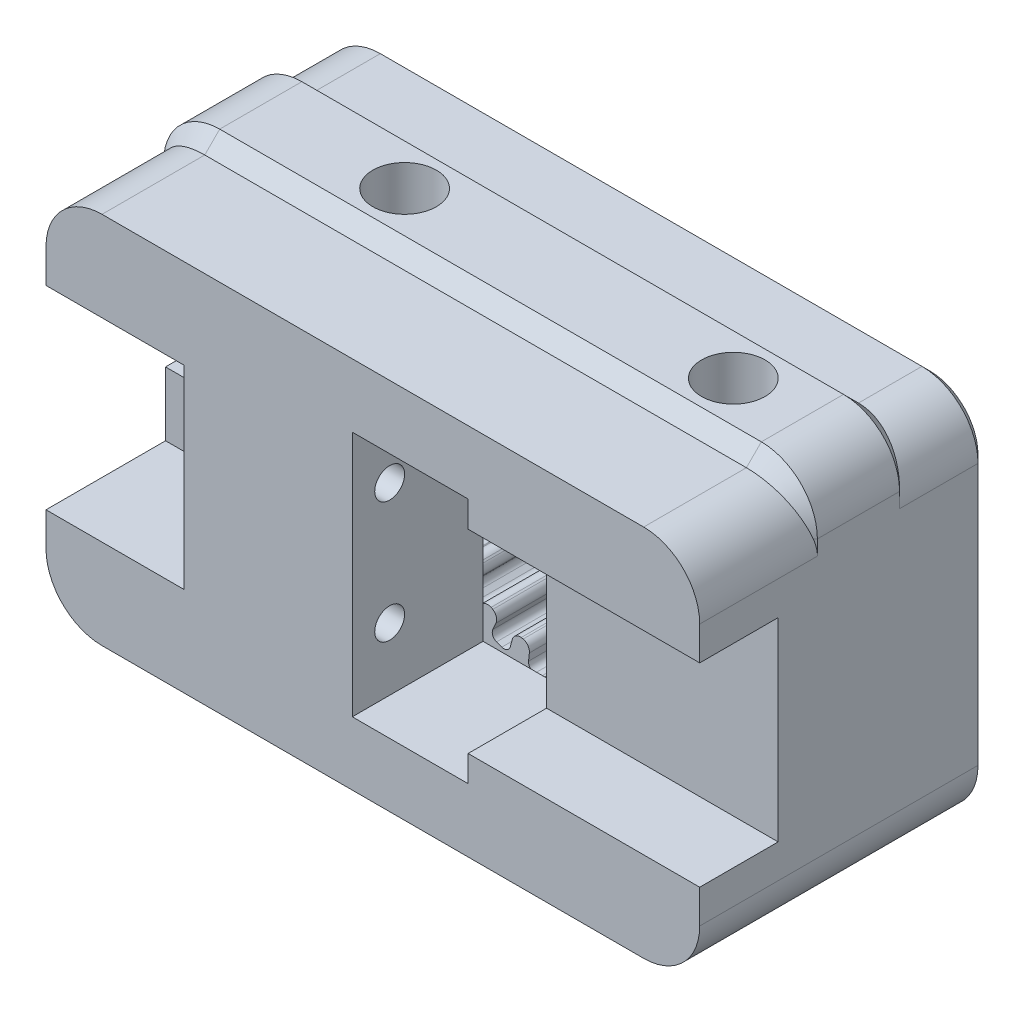
SolidWorks part; units mm, degrees
material "ABS"
ref_plane "Top Plane" through (0, 0, 0) normal (0, 0, 1) x (1, 0, 0)
ref_plane "Front Plane" through (0, 0, 0) normal (0, 1, 0) x (1, 0, 0)
ref_plane "Right Plane" through (0, 0, 0) normal (1, 0, 0) x (0, 0, -1)
sketch "Sketch1" plane through (0, 0, 0) normal (0, 0, 1) x (1, 0, 0)
  line L1 (-17.5, -10) -> (17.5, -10)
  line L2 (-17.5, -10) -> (-17.5, 10)
  line L3 (-17.5, 10) -> (17.5, 10)
  line L4 (17.5, -10) -> (17.5, 10)
  line L5 (-17.5, -10) -> (17.5, 10) construction
  line L6 (-17.5, 10) -> (17.5, -10) construction
  point P0 (0, 0)
  dimension "D1" = 35
  dimension "D2" = 20
extrude "Base" add sketch "Sketch1" along normal blind 15.3
sketch "Sketch2" plane through (0, 0, 15.3) normal (0, 0, 1) x (1, 0, 0)
  line L0 (-17.5, 10) -> (-17.5, -10) construction
  line L1 (-17.5, 5.2) -> (-10.1, 5.2)
  line L2 (-17.5, 5.2) -> (-17.5, -5.2)
  line L3 (-17.5, -5.2) -> (-10.1, -5.2)
  line L4 (-10.1, 5.2) -> (-10.1, -5.2)
  dimension "D1" = 7.4
  dimension "D2" = 10.4
  dimension "D3" = 5.2
extrude "plug cutout1" cut sketch "Sketch2" against normal blind 6.4
sketch "Sketch3" plane through (0, 0, 8.9) normal (0, 0, 1) x (1, 0, 0)
  line L0 (-17.5, 5.2) -> (-17.5, -5.2) construction
  line L1 (-17.5, 1.775) -> (-10.1, 1.775)
  line L2 (-17.5, 1.775) -> (-17.5, -1.775)
  line L3 (-17.5, -1.775) -> (-10.1, -1.775)
  line L4 (-10.1, 1.775) -> (-10.1, -1.775)
  line L5 (-10.1, -5.2) -> (-10.1, 5.2) construction
  dimension "D1" = 3.55
  dimension "D2" = 1.775
extrude "plug cutout 2" cut sketch "Sketch3" against normal blind 2.8
sketch "Sketch4" plane through (0, 0, 15.3) normal (0, 0, 1) x (1, 0, 0)
  line L0 (17.5, -10) -> (17.5, 10) construction
  line L1 (17.5, 5.2) -> (5.1, 5.2)
  line L2 (17.5, 5.2) -> (17.5, -5.2)
  line L3 (17.5, -5.2) -> (5.1, -5.2)
  line L4 (5.1, 5.2) -> (5.1, -5.2)
  dimension "D1" = 10.4
  dimension "D2" = 5.2
  dimension "D3" = 12.4
extrude "electronics cutout 1" cut sketch "Sketch4" against normal blind 4.2
sketch "Sketch5" plane through (0, 0, 15.3) normal (0, 0, 1) x (1, 0, 0)
  line L0 (5.1, 5.2) -> (5.1, -5.2) construction
  line L1 (-1.1, 6.6) -> (5.1, 6.6)
  line L2 (-1.1, 6.6) -> (-1.1, -6.6)
  line L3 (-1.1, -6.6) -> (5.1, -6.6)
  line L4 (5.1, 6.6) -> (5.1, -6.6)
  dimension "D1" = 6.2
  dimension "D2" = 13.2
  dimension "D3" = 6.6
  dimension "D4" = 0
extrude "switch cutout" cut sketch "Sketch5" against normal blind 7
sketch "Sketch6" plane through (-1.1, 0, 0) normal (1, 0, 0) x (0, 0, -1)
  line L0 (-15.3, 6.6) -> (-15.3, -6.6) construction
  circle A0 centre (-13.3, 3.25) radius 0.8
  circle A1 centre (-13.3, -3.25) radius 0.8
  dimension "D1" = 1.6
  dimension "D2" = 1.6
  dimension "D3" = 6.5
  dimension "D4" = 3.25
  dimension "D5" = 2
  dimension "D6" = 2
extrude "switch screwholes" cut sketch "Sketch6" against normal blind 4.5
sketch "Sketch7" plane through (0, 0, 0) normal (0, 0, -1) x (-1, 0, 0)
  circle A0 centre (-2, 0) radius 5.5
  dimension "D1" = 11
  dimension "D2" = 2
extrude "Cut-Extrude6" cut sketch "Sketch7" against normal blind 8.3
chamfer "Chamfer1" distance 1.2 angle 45 1 edges at (-3.5, 0, 0)
sketch "Sketch9" plane through (0, 0, 0) normal (0, 0, -1) x (-1, 0, 0)
  line L0 (-2, 0) -> (-2.1763, 6.6977) construction
  line L1 (-2, 0) -> (-0.098, 6.4243) construction
  line L2 (-2, 0) -> (-1.6503, 6.6909) construction
  line L3 (-2, 0) -> (-0.6079, 6.5538) construction
  line L4 (-1.6693, 6.3264) -> (-1.6904, 5.9232)
  line L5 (-0.6837, 6.1968) -> (-0.7676, 5.8019)
  line L6 (0.2695, 5.9146) -> (0.1248, 5.5376)
  line L7 (1.1668, 5.4868) -> (0.965, 5.1371)
  line L8 (1.9861, 4.9238) -> (1.7321, 4.61)
  line L9 (2.7073, 4.2396) -> (2.4073, 3.9694)
  line L10 (3.3126, 3.451) -> (2.974, 3.2311)
  line L11 (3.787, 2.5775) -> (3.4182, 2.4132)
  line L12 (4.119, 1.6405) -> (3.729, 1.5359)
  line L13 (4.3003, 0.663) -> (3.8987, 0.6208)
  line L14 (4.3264, -0.3307) -> (3.9232, -0.3096)
  line L15 (4.1968, -1.3163) -> (3.8019, -1.2324)
  line L16 (3.9146, -2.2695) -> (3.5376, -2.1248)
  line L17 (3.4868, -3.1668) -> (3.1371, -2.965)
  line L18 (2.9238, -3.9861) -> (2.61, -3.7321)
  line L19 (2.2396, -4.7073) -> (1.9694, -4.4073)
  line L20 (1.451, -5.3126) -> (1.2311, -4.974)
  line L21 (0.5775, -5.787) -> (0.4132, -5.4182)
  line L22 (-0.3595, -6.119) -> (-0.4641, -5.729)
  line L23 (-1.337, -6.3003) -> (-1.3792, -5.8987)
  line L24 (-2.3307, -6.3264) -> (-2.3096, -5.9232)
  line L25 (-3.3163, -6.1968) -> (-3.2324, -5.8019)
  line L26 (-4.2695, -5.9146) -> (-4.1248, -5.5376)
  line L27 (-5.1668, -5.4868) -> (-4.965, -5.1371)
  line L28 (-5.9861, -4.9238) -> (-5.7321, -4.61)
  line L29 (-6.7073, -4.2396) -> (-6.4073, -3.9694)
  line L30 (-7.3126, -3.451) -> (-6.974, -3.2311)
  line L31 (-7.787, -2.5775) -> (-7.4182, -2.4132)
  line L32 (-8.119, -1.6405) -> (-7.729, -1.5359)
  line L33 (-8.3003, -0.663) -> (-7.8987, -0.6208)
  line L34 (-8.3264, 0.3307) -> (-7.9232, 0.3096)
  line L35 (-8.1968, 1.3163) -> (-7.8019, 1.2324)
  line L36 (-7.9146, 2.2695) -> (-7.5376, 2.1248)
  line L37 (-7.4868, 3.1668) -> (-7.1371, 2.965)
  line L38 (-6.9238, 3.9861) -> (-6.61, 3.7321)
  line L39 (-6.2396, 4.7073) -> (-5.9694, 4.4073)
  line L40 (-5.451, 5.3126) -> (-5.2311, 4.974)
  line L41 (-4.5775, 5.787) -> (-4.4132, 5.4182)
  line L42 (-3.6405, 6.119) -> (-3.5359, 5.729)
  line L43 (-2.663, 6.3003) -> (-2.6208, 5.8987)
  circle A0 centre (-2, 0) radius 6.7 construction
  arc A1 (-2.1763, 6.6977) -> (-2.0251, 6.7) centre (-2, 0) cw
  arc A2 (-0.2434, 6.4656) -> (-0.098, 6.4243) centre (-2, 0) cw
  arc A3 (-1.2984, 5.4534) -> (-1.2677, 5.4494) centre (-2, 0) cw
  arc A4 (-0.2434, 6.4656) -> (-0.6837, 6.1968) centre (-0.3364, 6.123) ccw
  arc A5 (-2.0251, 6.7) -> (-1.6693, 6.3264) centre (-2.0238, 6.345) cw
  arc A6 (-1.2677, 5.4494) -> (-0.7676, 5.8019) centre (-1.2078, 5.8954) ccw
  arc A7 (-1.2984, 5.4534) -> (-1.6904, 5.9232) centre (-1.241, 5.8997) cw
  arc A8 (-0.098, 6.4243) -> (0.0465, 6.3798) centre (-2, 0) cw
  arc A9 (1.6686, 5.6063) -> (1.7942, 5.5222) centre (-2, 0) cw
  arc A10 (0.3524, 4.9697) -> (0.3804, 4.9564) centre (-2, 0) cw
  arc A11 (1.6686, 5.6063) -> (1.1668, 5.4868) centre (1.4743, 5.3093) ccw
  arc A12 (0.0465, 6.3798) -> (0.2695, 5.9146) centre (-0.062, 6.0418) cw
  arc A13 (0.3804, 4.9564) -> (0.965, 5.1371) centre (0.5752, 5.362) ccw
  arc A14 (0.3524, 4.9697) -> (0.1248, 5.5376) centre (0.545, 5.3764) cw
  arc A15 (1.7942, 5.5222) -> (1.9178, 5.4352) centre (-2, 0) cw
  arc A16 (3.2215, 4.1983) -> (3.3149, 4.0794) centre (-2, 0) cw
  arc A17 (1.773, 3.9995) -> (1.7955, 3.9782) centre (-2, 0) cw
  arc A18 (3.2215, 4.1983) -> (2.7073, 4.2396) centre (2.9449, 3.9758) ccw
  arc A19 (1.9178, 5.4352) -> (1.9861, 4.9238) centre (1.7102, 5.1472) cw
  arc A20 (1.7955, 3.9782) -> (2.4073, 3.9694) centre (2.1061, 4.3038) ccw
  arc A21 (1.773, 3.9995) -> (1.7321, 4.61) centre (2.0818, 4.3269) cw
  arc A22 (3.3149, 4.0794) -> (3.4056, 3.9585) centre (-2, 0) cw
  arc A23 (4.2633, 2.3793) -> (4.3154, 2.2374) centre (-2, 0) cw
  arc A24 (2.8243, 2.6378) -> (2.8391, 2.6106) centre (-2, 0) cw
  arc A25 (4.2633, 2.3793) -> (3.787, 2.5775) centre (3.9315, 2.2532) ccw
  arc A26 (3.4056, 3.9585) -> (3.3126, 3.451) centre (3.1192, 3.7487) cw
  arc A27 (2.8391, 2.6106) -> (3.4182, 2.4132) centre (3.2351, 2.8243) ccw
  arc A28 (2.8243, 2.6378) -> (2.974, 3.2311) centre (3.2191, 2.8537) cw
  arc A29 (4.3154, 2.2374) -> (4.3643, 2.0943) centre (-2, 0) cw
  arc A30 (4.692, 0.3273) -> (4.6977, 0.1763) centre (-2, 0) cw
  arc A31 (3.4033, 1.0179) -> (3.409, 0.9875) centre (-2, 0) cw
  arc A32 (4.692, 0.3273) -> (4.3003, 0.663) centre (4.3374, 0.31) ccw
  arc A33 (4.3643, 2.0943) -> (4.119, 1.6405) centre (4.0271, 1.9834) cw
  arc A34 (3.409, 0.9875) -> (3.8987, 0.6208) centre (3.8516, 1.0683) ccw
  arc A35 (3.4033, 1.0179) -> (3.729, 1.5359) centre (3.8455, 1.1013) cw
  arc A36 (4.6977, 0.1763) -> (4.7, 0.0251) centre (-2, 0) cw
  arc A37 (4.4656, -1.7566) -> (4.4243, -1.902) centre (-2, 0) cw
  arc A38 (3.4534, -0.7016) -> (3.4494, -0.7323) centre (-2, 0) cw
  arc A39 (4.4656, -1.7566) -> (4.1968, -1.3163) centre (4.123, -1.6636) ccw
  arc A40 (4.7, 0.0251) -> (4.3264, -0.3307) centre (4.345, 0.0238) cw
  arc A41 (3.4494, -0.7323) -> (3.8019, -1.2324) centre (3.8954, -0.7922) ccw
  arc A42 (3.4534, -0.7016) -> (3.9232, -0.3096) centre (3.8997, -0.759) cw
  arc A43 (4.4243, -1.902) -> (4.3798, -2.0465) centre (-2, 0) cw
  arc A44 (3.6063, -3.6686) -> (3.5222, -3.7942) centre (-2, 0) cw
  arc A45 (2.9697, -2.3524) -> (2.9564, -2.3804) centre (-2, 0) cw
  arc A46 (3.6063, -3.6686) -> (3.4868, -3.1668) centre (3.3093, -3.4743) ccw
  arc A47 (4.3798, -2.0465) -> (3.9146, -2.2695) centre (4.0418, -1.938) cw
  arc A48 (2.9564, -2.3804) -> (3.1371, -2.965) centre (3.362, -2.5752) ccw
  arc A49 (2.9697, -2.3524) -> (3.5376, -2.1248) centre (3.3764, -2.545) cw
  arc A50 (3.5222, -3.7942) -> (3.4352, -3.9178) centre (-2, 0) cw
  arc A51 (2.1983, -5.2215) -> (2.0794, -5.3149) centre (-2, 0) cw
  arc A52 (1.9995, -3.773) -> (1.9782, -3.7955) centre (-2, 0) cw
  arc A53 (2.1983, -5.2215) -> (2.2396, -4.7073) centre (1.9758, -4.9449) ccw
  arc A54 (3.4352, -3.9178) -> (2.9238, -3.9861) centre (3.1472, -3.7102) cw
  arc A55 (1.9782, -3.7955) -> (1.9694, -4.4073) centre (2.3038, -4.1061) ccw
  arc A56 (1.9995, -3.773) -> (2.61, -3.7321) centre (2.3269, -4.0818) cw
  arc A57 (2.0794, -5.3149) -> (1.9585, -5.4056) centre (-2, 0) cw
  arc A58 (0.3793, -6.2633) -> (0.2374, -6.3154) centre (-2, 0) cw
  arc A59 (0.6378, -4.8243) -> (0.6106, -4.8391) centre (-2, 0) cw
  arc A60 (0.3793, -6.2633) -> (0.5775, -5.787) centre (0.2532, -5.9315) ccw
  arc A61 (1.9585, -5.4056) -> (1.451, -5.3126) centre (1.7487, -5.1192) cw
  arc A62 (0.6106, -4.8391) -> (0.4132, -5.4182) centre (0.8243, -5.2351) ccw
  arc A63 (0.6378, -4.8243) -> (1.2311, -4.974) centre (0.8537, -5.2191) cw
  arc A64 (0.2374, -6.3154) -> (0.0943, -6.3643) centre (-2, 0) cw
  arc A65 (-1.6727, -6.692) -> (-1.8237, -6.6977) centre (-2, 0) cw
  arc A66 (-0.9821, -5.4033) -> (-1.0125, -5.409) centre (-2, 0) cw
  arc A67 (-1.6727, -6.692) -> (-1.337, -6.3003) centre (-1.69, -6.3374) ccw
  arc A68 (0.0943, -6.3643) -> (-0.3595, -6.119) centre (-0.0166, -6.0271) cw
  arc A69 (-1.0125, -5.409) -> (-1.3792, -5.8987) centre (-0.9317, -5.8516) ccw
  arc A70 (-0.9821, -5.4033) -> (-0.4641, -5.729) centre (-0.8987, -5.8455) cw
  arc A71 (-1.8237, -6.6977) -> (-1.9749, -6.7) centre (-2, 0) cw
  arc A72 (-3.7566, -6.4656) -> (-3.902, -6.4243) centre (-2, 0) cw
  arc A73 (-2.7016, -5.4534) -> (-2.7323, -5.4494) centre (-2, 0) cw
  arc A74 (-3.7566, -6.4656) -> (-3.3163, -6.1968) centre (-3.6636, -6.123) ccw
  arc A75 (-1.9749, -6.7) -> (-2.3307, -6.3264) centre (-1.9762, -6.345) cw
  arc A76 (-2.7323, -5.4494) -> (-3.2324, -5.8019) centre (-2.7922, -5.8954) ccw
  arc A77 (-2.7016, -5.4534) -> (-2.3096, -5.9232) centre (-2.759, -5.8997) cw
  arc A78 (-3.902, -6.4243) -> (-4.0465, -6.3798) centre (-2, 0) cw
  arc A79 (-5.6686, -5.6063) -> (-5.7942, -5.5222) centre (-2, 0) cw
  arc A80 (-4.3524, -4.9697) -> (-4.3804, -4.9564) centre (-2, 0) cw
  arc A81 (-5.6686, -5.6063) -> (-5.1668, -5.4868) centre (-5.4743, -5.3093) ccw
  arc A82 (-4.0465, -6.3798) -> (-4.2695, -5.9146) centre (-3.938, -6.0418) cw
  arc A83 (-4.3804, -4.9564) -> (-4.965, -5.1371) centre (-4.5752, -5.362) ccw
  arc A84 (-4.3524, -4.9697) -> (-4.1248, -5.5376) centre (-4.545, -5.3764) cw
  arc A85 (-5.7942, -5.5222) -> (-5.9178, -5.4352) centre (-2, 0) cw
  arc A86 (-7.2215, -4.1983) -> (-7.3149, -4.0794) centre (-2, 0) cw
  arc A87 (-5.773, -3.9995) -> (-5.7955, -3.9782) centre (-2, 0) cw
  arc A88 (-7.2215, -4.1983) -> (-6.7073, -4.2396) centre (-6.9449, -3.9758) ccw
  arc A89 (-5.9178, -5.4352) -> (-5.9861, -4.9238) centre (-5.7102, -5.1472) cw
  arc A90 (-5.7955, -3.9782) -> (-6.4073, -3.9694) centre (-6.1061, -4.3038) ccw
  arc A91 (-5.773, -3.9995) -> (-5.7321, -4.61) centre (-6.0818, -4.3269) cw
  arc A92 (-7.3149, -4.0794) -> (-7.4056, -3.9585) centre (-2, 0) cw
  arc A93 (-8.2633, -2.3793) -> (-8.3154, -2.2374) centre (-2, 0) cw
  arc A94 (-6.8243, -2.6378) -> (-6.8391, -2.6106) centre (-2, 0) cw
  arc A95 (-8.2633, -2.3793) -> (-7.787, -2.5775) centre (-7.9315, -2.2532) ccw
  arc A96 (-7.4056, -3.9585) -> (-7.3126, -3.451) centre (-7.1192, -3.7487) cw
  arc A97 (-6.8391, -2.6106) -> (-7.4182, -2.4132) centre (-7.2351, -2.8243) ccw
  arc A98 (-6.8243, -2.6378) -> (-6.974, -3.2311) centre (-7.2191, -2.8537) cw
  arc A99 (-8.3154, -2.2374) -> (-8.3643, -2.0943) centre (-2, 0) cw
  arc A100 (-8.692, -0.3273) -> (-8.6977, -0.1763) centre (-2, 0) cw
  arc A101 (-7.4033, -1.0179) -> (-7.409, -0.9875) centre (-2, 0) cw
  arc A102 (-8.692, -0.3273) -> (-8.3003, -0.663) centre (-8.3374, -0.31) ccw
  arc A103 (-8.3643, -2.0943) -> (-8.119, -1.6405) centre (-8.0271, -1.9834) cw
  arc A104 (-7.409, -0.9875) -> (-7.8987, -0.6208) centre (-7.8516, -1.0683) ccw
  arc A105 (-7.4033, -1.0179) -> (-7.729, -1.5359) centre (-7.8455, -1.1013) cw
  arc A106 (-8.6977, -0.1763) -> (-8.7, -0.0251) centre (-2, 0) cw
  arc A107 (-8.4656, 1.7566) -> (-8.4243, 1.902) centre (-2, 0) cw
  arc A108 (-7.4534, 0.7016) -> (-7.4494, 0.7323) centre (-2, 0) cw
  arc A109 (-8.4656, 1.7566) -> (-8.1968, 1.3163) centre (-8.123, 1.6636) ccw
  arc A110 (-8.7, -0.0251) -> (-8.3264, 0.3307) centre (-8.345, -0.0238) cw
  arc A111 (-7.4494, 0.7323) -> (-7.8019, 1.2324) centre (-7.8954, 0.7922) ccw
  arc A112 (-7.4534, 0.7016) -> (-7.9232, 0.3096) centre (-7.8997, 0.759) cw
  arc A113 (-8.4243, 1.902) -> (-8.3798, 2.0465) centre (-2, 0) cw
  arc A114 (-7.6063, 3.6686) -> (-7.5222, 3.7942) centre (-2, 0) cw
  arc A115 (-6.9697, 2.3524) -> (-6.9564, 2.3804) centre (-2, 0) cw
  arc A116 (-7.6063, 3.6686) -> (-7.4868, 3.1668) centre (-7.3093, 3.4743) ccw
  arc A117 (-8.3798, 2.0465) -> (-7.9146, 2.2695) centre (-8.0418, 1.938) cw
  arc A118 (-6.9564, 2.3804) -> (-7.1371, 2.965) centre (-7.362, 2.5752) ccw
  arc A119 (-6.9697, 2.3524) -> (-7.5376, 2.1248) centre (-7.3764, 2.545) cw
  arc A120 (-7.5222, 3.7942) -> (-7.4352, 3.9178) centre (-2, 0) cw
  arc A121 (-6.1983, 5.2215) -> (-6.0794, 5.3149) centre (-2, 0) cw
  arc A122 (-5.9995, 3.773) -> (-5.9782, 3.7955) centre (-2, 0) cw
  arc A123 (-6.1983, 5.2215) -> (-6.2396, 4.7073) centre (-5.9758, 4.9449) ccw
  arc A124 (-7.4352, 3.9178) -> (-6.9238, 3.9861) centre (-7.1472, 3.7102) cw
  arc A125 (-5.9782, 3.7955) -> (-5.9694, 4.4073) centre (-6.3038, 4.1061) ccw
  arc A126 (-5.9995, 3.773) -> (-6.61, 3.7321) centre (-6.3269, 4.0818) cw
  arc A127 (-6.0794, 5.3149) -> (-5.9585, 5.4056) centre (-2, 0) cw
  arc A128 (-4.3793, 6.2633) -> (-4.2374, 6.3154) centre (-2, 0) cw
  arc A129 (-4.6378, 4.8243) -> (-4.6106, 4.8391) centre (-2, 0) cw
  arc A130 (-4.3793, 6.2633) -> (-4.5775, 5.787) centre (-4.2532, 5.9315) ccw
  arc A131 (-5.9585, 5.4056) -> (-5.451, 5.3126) centre (-5.7487, 5.1192) cw
  arc A132 (-4.6106, 4.8391) -> (-4.4132, 5.4182) centre (-4.8243, 5.2351) ccw
  arc A133 (-4.6378, 4.8243) -> (-5.2311, 4.974) centre (-4.8537, 5.2191) cw
  arc A134 (-4.2374, 6.3154) -> (-4.0943, 6.3643) centre (-2, 0) cw
  arc A135 (-2.3273, 6.692) -> (-2.1763, 6.6977) centre (-2, 0) cw
  arc A136 (-3.0179, 5.4033) -> (-2.9875, 5.409) centre (-2, 0) cw
  arc A137 (-2.3273, 6.692) -> (-2.663, 6.3003) centre (-2.31, 6.3374) ccw
  arc A138 (-4.0943, 6.3643) -> (-3.6405, 6.119) centre (-3.9834, 6.0271) cw
  arc A139 (-2.9875, 5.409) -> (-2.6208, 5.8987) centre (-3.0683, 5.8516) ccw
  arc A140 (-3.0179, 5.4033) -> (-3.5359, 5.729) centre (-3.1013, 5.8455) cw
  point P0 (-2, 0)
  point P19 (-0.8576, 5.3784)
  point P22 (-1.713, 5.4909)
  circle M1 centre (-2, 0) radius 6.7
  dimension "D5" = 0.355
  dimension "D6" = 0.45
  dimension "D1" = 18
  dimension "D2" = 9
  dimension "D3" = 4.5
  dimension "D4" = 1.2
  dimension "D7" = 20
extrude "Cut-Extrude7" cut sketch "Sketch9" against normal blind 8.3 contours A136 A140 L42 A138 A130 L41 A132 A129 A133 L40 A131 A123 L39 A125 A122 A126 L38 A124 A116 L37 A118 A115 A119 L36 A117 A109 L35 A111 A108 A112 L34 A110 A102 L33 A104 A101 A105 L32 A103 M1 region at (2, 0, 0)
sketch "Sketch11" plane through (0, 10, 0) normal (0, 1, 0) x (1, 0, 0)
  line L0 (-17.5, -15.3) -> (-17.5, 0) construction
  line L1 (-17.5, -3.8) -> (17.5, -3.8)
  line L2 (-17.5, -3.8) -> (-17.5, -9.8)
  line L3 (-17.5, -9.8) -> (17.5, -9.8)
  line L4 (17.5, -3.8) -> (17.5, -9.8)
  line L5 (17.5, -15.3) -> (17.5, 0) construction
  line L6 (17.5, 0) -> (-17.5, 0) construction
  dimension "D1" = 6
  dimension "D2" = 3.8
extrude "Boss-Extrude2" add sketch "Sketch11" along normal blind 0.8
sketch "Sketch10" plane through (0, -10, 0) normal (0, -1, 0) x (1, 0, 0)
  line L0 (-17.5, 0) -> (17.5, 0) construction
  line L1 (17.5, 15.3) -> (17.5, 0) construction
  line L2 (-17.5, 15.3) -> (-17.5, 0) construction
  circle A0 centre (-6.8, 6.8) radius 1.7
  circle A1 centre (10.8, 6.8) radius 1.7
  dimension "D1" = 3.4
  dimension "D2" = 3.4
  dimension "D3" = 6.8
  dimension "D4" = 6.8
  dimension "D5" = 6.7
  dimension "D6" = 10.7
extrude "Cut-Extrude8" cut sketch "Sketch10" against normal through all
sketch "Sketch12" plane through (0, -10, 0) normal (0, -1, 0) x (1, 0, 0)
  circle A0 centre (-6.8, 6.8) radius 2.85
  circle A1 centre (10.8, 6.8) radius 2.85
  dimension "D1" = 5.7
  dimension "D2" = 5.7
extrude "Cut-Extrude9" cut sketch "Sketch12" against normal blind 3.1
fillet "Fillet1" radius 3 6 edges at (-17.5, 10, 12.55) (-17.5, 10, 1.9) (17.5, 10, 1.9) (17.5, 10, 12.55) (-17.5, -10, 7.65) (17.5, -10, 7.65)
fillet "Fillet2" radius 3 2 edges at (-17.5, 10.8, 6.8) (17.5, 10.8, 6.8)
chamfer "Chamfer2" distance 0.8 angle 45 10 edges at (0, 10.8, 3.8) (0, 10.8, 9.8) (17.5, 7.4, 3.8) (-17.5, 7.4, 3.8) (16.6213, 9.9213, 3.8) (-16.6213, 9.9213, 3.8) (-17.5, 7.4, 9.8) (17.5, 7.4, 9.8) (-16.6213, 9.9213, 9.8) (16.6213, 9.9213, 9.8)
chamfer "Chamfer3" distance 0.4 angle 45 10 edges at (-6.8, -10, 3.95) (10.8, -10, 3.95) (0, 10, 0) (-16.6213, 9.1213, 0) (16.6213, 9.1213, 0) (-17.5, 0, 0) (17.5, 0, 0) (-16.6213, -9.1213, 0) (16.6213, -9.1213, 0) (0, -10, 0)
